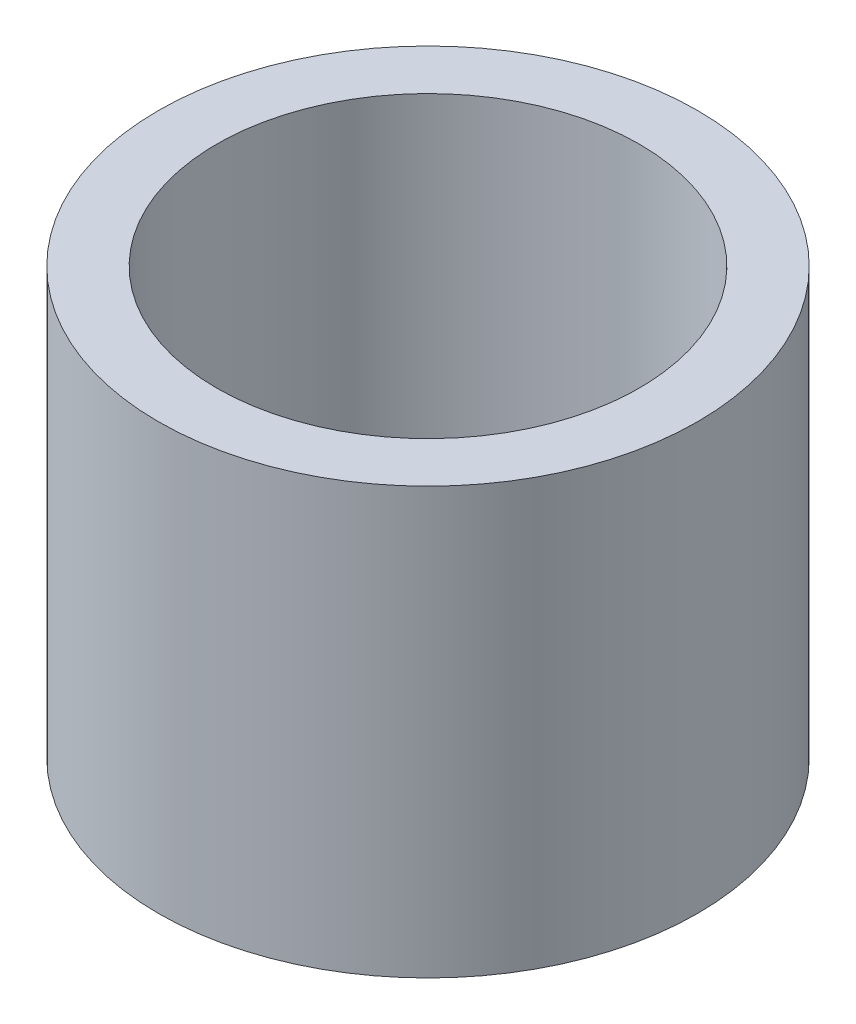
SolidWorks part; units mm, degrees
material "PET"
ref_plane "Front Plane" through (0, 0, 0) normal (0, 0, 1) x (1, 0, 0)
ref_plane "Top Plane" through (0, 0, 0) normal (0, 1, 0) x (1, 0, 0)
ref_plane "Right Plane" through (0, 0, 0) normal (1, 0, 0) x (0, 0, -1)
sketch "Sketch1" plane through (0, 0, 0) normal (0, 1, 0) x (1, 0, 0)
  circle A0 centre (0, 0) radius 3.175
  circle A1 centre (0, 0) radius 2.4892
  dimension "D1" = 6.35
  dimension "D2" = 4.9784
extrude "Boss-Extrude1" add sketch "Sketch1" along normal blind 5.0165
